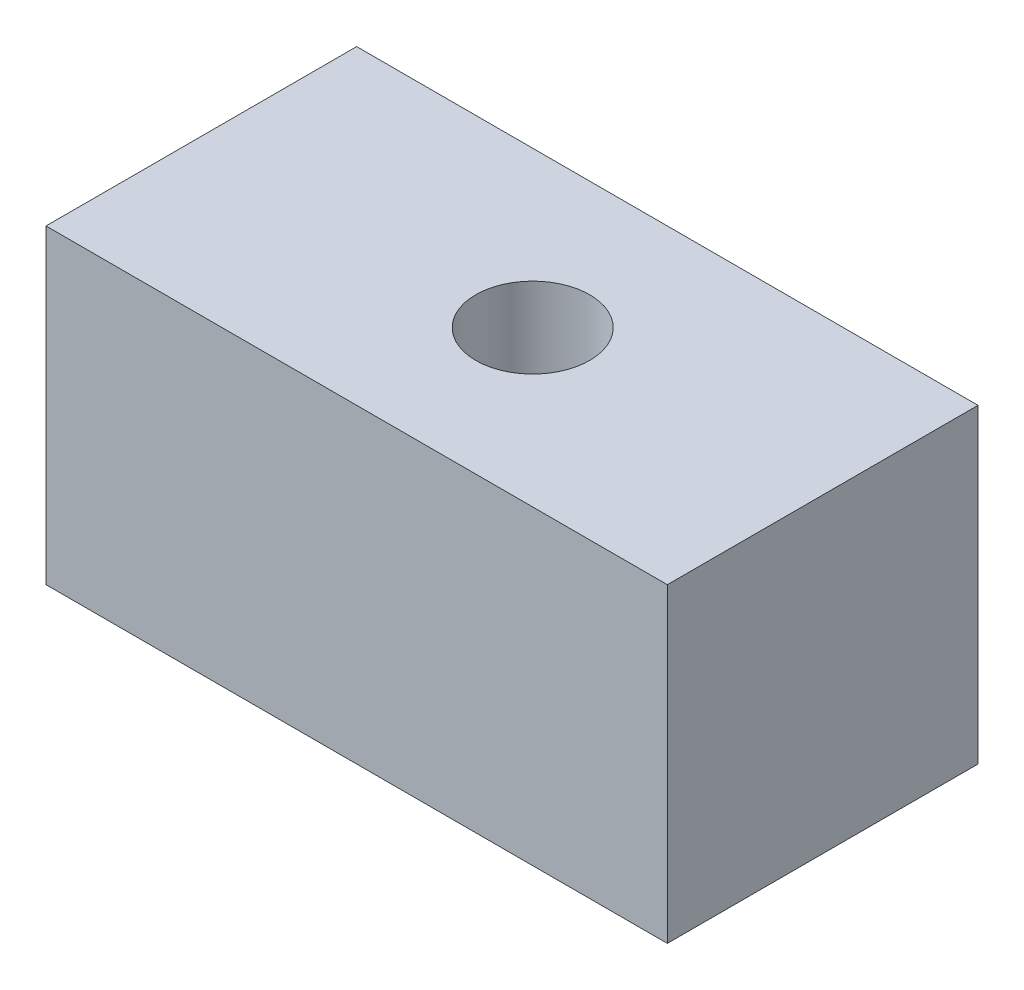
SolidWorks part; units mm, degrees
ref_plane "Front Plane" through (0, 0, 0) normal (0, 0, 1) x (1, 0, 0)
ref_plane "Top Plane" through (0, 0, 0) normal (0, 1, 0) x (1, 0, 0)
ref_plane "Right Plane" through (0, 0, 0) normal (1, 0, 0) x (0, 0, -1)
sketch "Sketch1" plane through (0, 0, 0) normal (1, 0, 0) x (0, 0, -1)
  line L1 (-7.5, 7.5) -> (7.5, 7.5)
  line L2 (-7.5, 7.5) -> (-7.5, -7.5)
  line L3 (-7.5, -7.5) -> (7.5, -7.5)
  line L4 (7.5, 7.5) -> (7.5, -7.5)
  line L5 (-7.5, 7.5) -> (7.5, -7.5) construction
  line L6 (-7.5, -7.5) -> (7.5, 7.5) construction
  point P0 (0, 0)
  dimension "D1" = 15
  dimension "D2" = 15
extrude "Boss-Extrude1" add sketch "Sketch1" along normal blind 30
sketch "Sketch2" plane through (0, 7.5, 0) normal (0, 1, 0) x (1, 0, 0)
  line L0 (0, 7.5) -> (0, -7.5) construction
  circle A0 centre (16, 0) radius 2.75
  dimension "D1" = 5.5
  dimension "D2" = 16
extrude "Cut-Extrude1" cut sketch "Sketch2" against normal through all
sketch "Sketch3" plane through (0, 0, -7.5) normal (0, 0, -1) x (-1, 0, 0)
  line L0 (0, -7.5) -> (0, 7.5) construction
  line L1 (0, 5.5) -> (-10, 5.5)
  line L2 (0, 5.5) -> (0, -1.358)
  line L3 (0, -1.358) -> (-10, -1.358)
  line L4 (-10, 5.5) -> (-10, -1.358)
  line L5 (-10, 2.071) -> (-4.92, 2.071) construction
  line L6 (-30, 7.5) -> (0, 7.5) construction
  circle A0 centre (-4.92, 2.071) radius 1.5875
  dimension "D2" = 3.175
  dimension "D1" = 6.858
  dimension "D3" = 5.08
  dimension "D4" = 10
  dimension "D5" = 2
extrude "Cut-Extrude2" cut sketch "Sketch3" against normal blind 1
